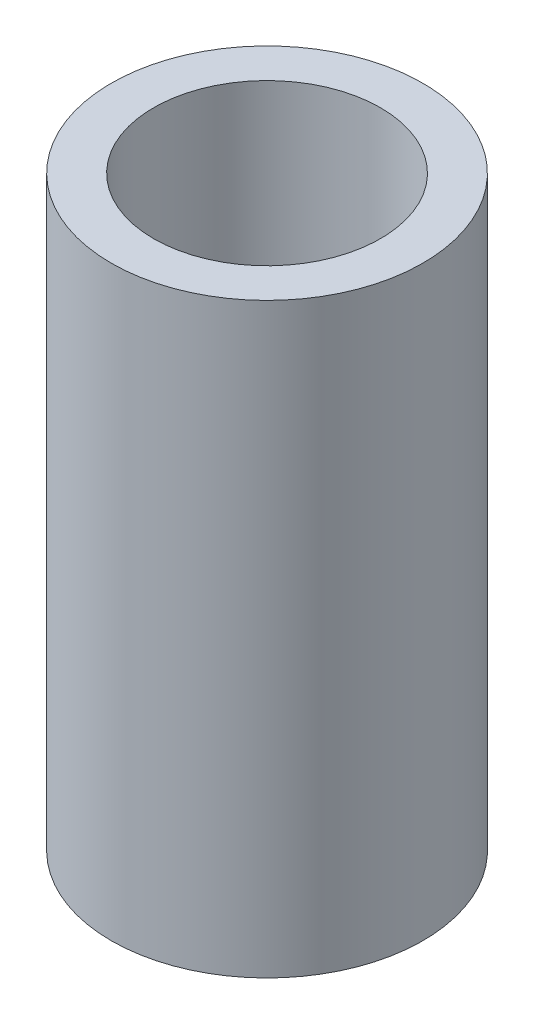
SolidWorks part; units mm, degrees
ref_plane "Front Plane" through (0, 0, 0) normal (0, 0, 1) x (1, 0, 0)
ref_plane "Top Plane" through (0, 0, 0) normal (0, 1, 0) x (1, 0, 0)
ref_plane "Right Plane" through (0, 0, 0) normal (1, 0, 0) x (0, 0, -1)
sketch "Sketch1" plane through (0, 0, 0) normal (0, 1, 0) x (1, 0, 0)
  circle A0 centre (0, 0) radius 17.5
  dimension "SLEEVE_OD" = 35
extrude "Boss-Extrude1" add sketch "Sketch1" along normal blind 65.8936
sketch "Sketch2" plane through (0, 0, 0) normal (0, 1, 0) x (1, 0, 0)
  circle A0 centre (0, 0) radius 12.7399
  dimension "BORE_D" = 25.4797
extrude "Cut-Extrude1" cut sketch "Sketch2" along normal through all
chamfer "Chamfer1" distance 3.4597 angle 45 rebuild error yes
